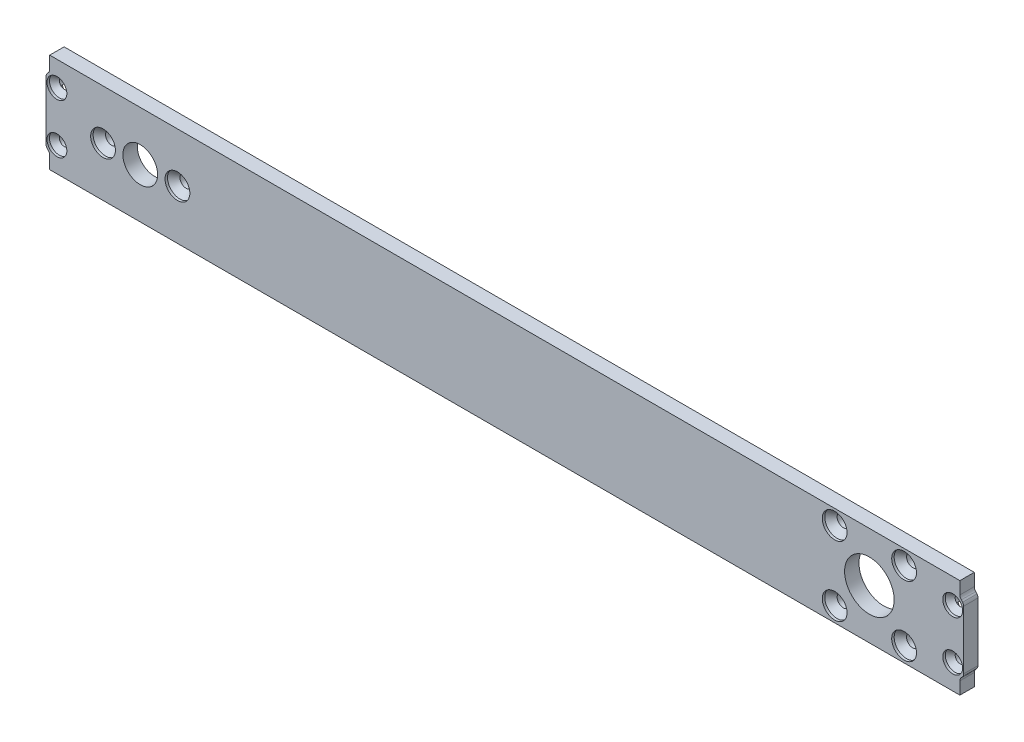
SolidWorks part; units mm, degrees
ref_plane "Front Plane" through (0, 0, 0) normal (0, 0, 1) x (1, 0, 0)
ref_plane "Top Plane" through (0, 0, 0) normal (0, 1, 0) x (1, 0, 0)
ref_plane "Right Plane" through (0, 0, 0) normal (1, 0, 0) x (0, 0, -1)
sketch "Sketch1" plane through (0, 0, 0) normal (0, 0, 1) x (1, 0, 0)
  line L1 (-92.5, 10) -> (92.5, 10)
  line L2 (-92.5, 10) -> (-92.5, -10)
  line L3 (-92.5, -10) -> (92.5, -10)
  line L4 (92.5, 10) -> (92.5, -10)
  line L5 (-92.5, 10) -> (92.5, -10) construction
  line L6 (-92.5, -10) -> (92.5, 10) construction
  point P0 (0, 0)
  dimension "D1" = 20
  dimension "D2" = 185
extrude "Base shape" add sketch "Sketch1" against normal blind 2.9
sketch "Sketch2" plane through (0, 0, 0) normal (0, 0, 1) x (1, 0, 0)
  line L0 (-83.5, 10) -> (-83.5, -10) construction
  line L1 (92.5, 10) -> (-92.5, 10) construction
  line L2 (-92.5, -10) -> (92.5, -10) construction
  line L3 (-92.5, 10) -> (-92.5, -10) construction
  line L4 (-92.5, 0) -> (92.5, 0) construction
  line L5 (92.5, -10) -> (92.5, 10) construction
  line L6 (-73.5, 10) -> (-73.5, -10) construction
  line L7 (0, 10) -> (0, -10) construction
  line L8 (73.5, 5) -> (92.5, 5) construction
  line L9 (-73.5, 3.5) -> (-92.5, 3.5) construction
  line L11 (80.5, -7) -> (66.5, -7)
  line L12 (80.5, -7) -> (80.5, 7)
  line L13 (80.5, 7) -> (66.5, 7)
  line L14 (66.5, -7) -> (66.5, 7)
  line L15 (80.5, -7) -> (66.5, 7) construction
  line L16 (80.5, 7) -> (66.5, -7) construction
  circle A0 centre (-73.5, 0) radius 10
  circle A1 centre (-81, 0) radius 1.25
  circle A2 centre (-66, 0) radius 1.25
  circle A3 centre (-73.5, 0) radius 3.5
  circle A4 centre (73.5, 0) radius 5
  circle A5 centre (66.5, 7) radius 1.25
  circle A6 centre (80.5, 7) radius 1.25
  circle A7 centre (80.5, -7) radius 1.25
  circle A8 centre (66.5, -7) radius 1.25
  dimension "D2" = 20
  dimension "D3" = 2.5
  dimension "D4" = 15
  dimension "D5" = 7
  dimension "D6" = 10
  dimension "D8" = 2.5
  dimension "D1" = 147
  dimension "D7" = 14
extrude "Motor cutouts" cut sketch "Sketch2" against normal up to next contours A5 | A6 | A7 | A8 | A1 | A2 | A3 | A4
hole_wizard "Motor M2.5 countersunks" positions "Sketch3" profile "Sketch4" countersink size "M2.5" standard "ANSI Metric" end condition through all
sketch "Sketch3" plane through (0, 0, 0) normal (0, 0, 1) x (1, 0, 0)
  point P0 (-81, 0)
  point P3 (-66, 0)
  point P7 (66.5, 7)
  point P10 (80.5, 7)
  point P13 (66.5, -7)
  point P16 (80.5, -7)
sketch "Sketch4" plane through (-81, 0, 0) normal (1, 0, 0) x (0, -1, 0)
  line L0 (0, 0) -> (0, 2.9)
  line L1 (0, 2.9) -> (1.25, 2.9)
  line L2 (1.25, 2.9) -> (1.25, 1.75)
  line L3 (1.25, 1.75) -> (2.5, 0.5)
  line L4 (2.5, 0.5) -> (2.5, 0)
  line L6 (2.5, 0) -> (0, 0)
  line L7 (-1.25, 1.75) -> (-2.5, 0.5) construction
  line L11 (0, -6.35) -> (0, 107.95) construction
  dimension "Thru Hole Dia." = 2.5
  dimension "Thru Hole Depth" = 2.9
  dimension "C'Sink Dia." = 5
  dimension "C'Sink Angle" = 90
  dimension "Head Clearance" = 0.5
sketch "Sketch5" plane through (0, 0, -2.9) normal (0, 0, -1) x (-1, 0, 0)
  line L0 (0, 10) -> (0, -10) construction
  line L3 (-92.5, 10) -> (92.5, 10) construction
  line L4 (92.5, -10) -> (-92.5, -10) construction
  line L5 (-60, -7) -> (60, -7) construction
  line L6 (-60, -6) -> (60, -6)
  line L7 (-60, -8) -> (60, -8)
  arc A0 (-60, -6) -> (-60, -8) centre (-60, -7) ccw
  arc A1 (60, -8) -> (60, -6) centre (60, -7) ccw
  point P8 (0, -7)
  dimension "D1" = 120
  dimension "D2" = 2
  dimension "D3" = 2
extrude "PCB slot" cut sketch "Sketch5" against normal blind 0.775
sketch "Sketch6" plane through (0, 0, 0) normal (0, 0, 1) x (1, 0, 0)
  line L0 (90.3, 10) -> (90.3, -10) construction
  line L1 (92.5, 10) -> (-92.5, 10) construction
  line L2 (-92.5, -10) -> (92.5, -10) construction
  line L3 (92.5, -10) -> (92.5, 10) construction
  line L4 (92.5, 0) -> (-92.5, 0) construction
  line L5 (-92.5, 10) -> (-92.5, -10) construction
  line L6 (0, 10) -> (0, -10) construction
  circle A0 centre (90.3, 5) radius 1
  circle A2 centre (90.3, -5) radius 1
  circle A3 centre (-90.3, -5) radius 1
  circle A5 centre (-90.3, 5) radius 1
  dimension "D2" = 2
  dimension "D1" = 2.2
  dimension "D3" = 10
extrude "End plate holes" cut sketch "Sketch6" against normal up to next
hole_wizard "CSK for M2 Flat Head Machine Screw3" positions "Sketch10" profile "Sketch9" countersink size "M2" standard "ANSI Metric" end condition through all
sketch "Sketch10" plane through (0, 0, 0) normal (0, 0, 1) x (1, 0, 0)
  point P2 (90.3, 5)
  point P8 (90.3, -5)
  point P11 (-90.3, 5)
  point P17 (-90.3, -5)
  point P23 (0, 0)
  point P24 (0, 0)
sketch "Sketch9" plane through (90.3, 5, 0) normal (1, 0, 0) x (0, -1, 0)
  line L0 (0, 0) -> (0, 2.9)
  line L1 (0, 2.9) -> (1, 2.9)
  line L2 (1, 2.9) -> (1, 1.5)
  line L3 (1, 1.5) -> (2, 0.5)
  line L4 (2, 0.5) -> (2, 0)
  line L6 (2, 0) -> (0, 0)
  line L7 (-1, 1.5) -> (-2, 0.5) construction
  line L11 (0, -6.35) -> (0, 107.95) construction
  dimension "Thru Hole Dia." = 2
  dimension "Thru Hole Depth" = 2.9
  dimension "C'Sink Dia." = 4
  dimension "C'Sink Angle" = 90
  dimension "Head Clearance" = 0.5
sketch "Sketch12" plane through (0, 0, -2.9) normal (0, 0, -1) x (-1, 0, 0)
  line L0 (-92.5, 0) -> (92.5, 0) construction
  line L1 (-92.5, -10) -> (-92.5, 10) construction
  line L2 (92.5, 10) -> (92.5, -10) construction
  line L3 (-90.3, 5) -> (-90.3, -5) construction
  line L4 (-88.8, 4) -> (-91.8, 1) construction
  line L5 (-91.8, 4) -> (-88.8, 4)
  line L6 (-91.8, 4) -> (-91.8, -4)
  line L7 (-91.8, -4) -> (-88.8, -4)
  line L8 (-88.8, 4) -> (-88.8, -4)
  line L9 (-91.8, 4) -> (-88.8, -4) construction
  line L10 (-91.8, -4) -> (-88.8, 4) construction
  line L11 (0, 10) -> (0, -10) construction
  line L12 (-92.5, 10) -> (92.5, 10) construction
  line L13 (92.5, -10) -> (-92.5, -10) construction
  line L14 (91.8, -4) -> (88.8, -4)
  line L15 (91.8, 4) -> (88.8, 4)
  line L16 (91.8, 4) -> (91.8, -4)
  line L17 (88.8, 4) -> (88.8, -4)
  circle A0 centre (-89.5071, 3.2929) radius 1
  circle A1 centre (-91.0929, 3.2929) radius 1
  circle A2 centre (-89.5071, -3.2929) radius 1
  circle A3 centre (-91.0929, -3.2929) radius 1
  circle A4 centre (89.5071, -3.2929) radius 1
  circle A5 centre (91.0929, -3.2929) radius 1
  circle A6 centre (89.5071, 3.2929) radius 1
  circle A7 centre (91.0929, 3.2929) radius 1
  point P10 (-90.3, 0)
  circle M9 centre (-90.3, -5) radius 1
  circle M10 centre (90.3, -5) radius 1
  circle M11 centre (90.3, 5) radius 1
  circle M12 centre (-90.3, 5) radius 1
  dimension "D3" = 2
  dimension "D1" = 3
  dimension "D2" = 8
  dimension "D4" = 45
extrude "Tap slots" cut sketch "Sketch12" against normal blind 1.4 contours A7 A6 M11 | A5 A4 M10 | A3 A2 M9 | A1 A0 M12 | A1 L5 M12 | A0 L5 M12 | A3 L7 M9 | A2 L7 M9 | A6 L15 M11 | A7 L15 M11 | A4 L14 M10 | A5 L14 M10 | A1 | A0 | A2 | A3 | L6 L7 L8 L5 | L17 L14 L16 L15 | A6 | A7 | A5 | A4 region at (90.3659, 4.0012, -2.9) region at (90.3, 5.03, -2.9) region at (90.2341, 4.0012, -2.9) region at (90.3659, -4.0012, -2.9) region at (90.3, -5.03, -2.9) region at (90.2341, -4.0012, -2.9) region at (-90.3659, -4.0012, -2.9) region at (-90.3, -5.03, -2.9) region at (-90.2341, -4.0012, -2.9) region at (-90.3659, 4.0012, -2.9) region at (-90.3, 5.03, -2.9) region at (-90.2341, 4.0012, -2.9)
sketch "Sketch13" plane through (0, 0, 0) normal (0, 0, 1) x (1, 0, 0)
  line L0 (-92.5, -10) -> (92.5, -10) construction
  line L1 (-92.5, 10) -> (-91.75, 10)
  line L2 (-92.5, 10) -> (-92.5, -10)
  line L3 (-92.5, -10) -> (-91.75, -10)
  line L4 (-91.75, 10) -> (-91.75, -10)
  line L5 (-92.5, 0) -> (92.5, 0) construction
  line L6 (92.5, -10) -> (92.5, 10) construction
  line L7 (0, 10) -> (0, -10) construction
  line L8 (92.5, 10) -> (-92.5, 10) construction
  line L9 (92.5, -10) -> (91.75, -10)
  line L10 (91.75, 10) -> (91.75, -10)
  line L11 (92.5, 10) -> (91.75, 10)
  line L12 (92.5, 10) -> (92.5, -10)
  circle A0 centre (-90.3, 5) radius 2.5
  circle A1 centre (-90.3, -5) radius 2.5
  circle A2 centre (90.3, 5) radius 2.5
  circle A3 centre (90.3, -5) radius 2.5
  line M16 (92.5, -10) -> (92.5, 10)
  line M17 (92.5, 10) -> (-92.5, 10)
  line M18 (-92.5, 10) -> (-92.5, -10)
  line M19 (-92.5, -10) -> (92.5, -10)
  dimension "D2" = 5
  dimension "D1" = 0.75
extrude "Cut-Extrude3" cut sketch "Sketch13" against normal up to next contours A0 L4 M17 M18 | A1 L4 M18 M19 | L10 A2 M16 M17 | A3 L10 M16 M19 region at (-92.1406, 8.3301, 0) region at (92.1406, 8.3301, 0) region at (-92.1406, -8.3301, 0) region at (92.1406, -8.3301, 0)
fillet "Fillet1" radius 1 8 edges at (-91.75, -7.0365, -1.45) (-92.5, -6.1874, -1.45) (-92.5, 6.1874, -1.45) (-91.75, 7.0365, -1.45) (92.5, 6.1874, -1.45) (91.75, 7.0365, -1.45) (92.5, -6.1874, -1.45) (91.75, -7.0365, -1.45)
